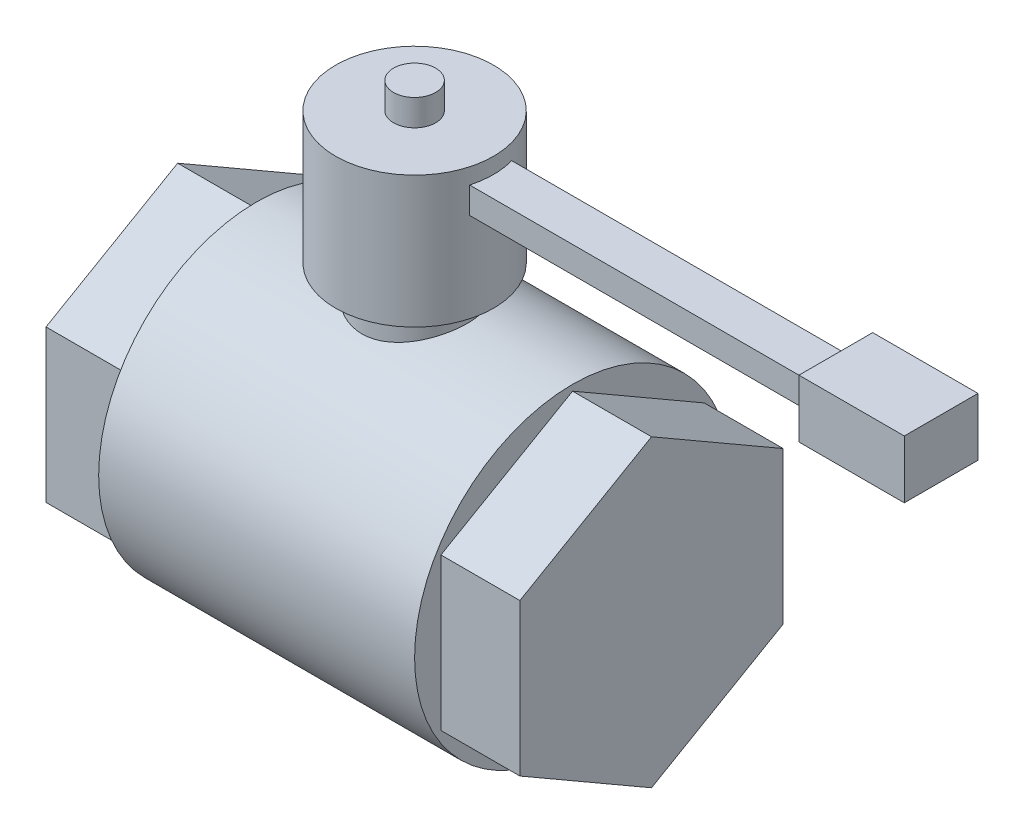
SolidWorks part; units mm, degrees
ref_plane "Плоскость1" through (0, 0, 0) normal (0, 0, 1) x (1, 0, 0)
ref_plane "Плоскость2" through (0, 0, 0) normal (0, 1, 0) x (1, 0, 0)
ref_plane "Плоскость3" through (0, 0, 0) normal (1, 0, 0) x (0, 0, -1)
sketch "Эскиз1" plane through (0, 0, 0) normal (1, 0, 0) x (0, 0, -1)
  line L1 (0, 28.8675) -> (-25, 14.4338)
  line L2 (-25, 14.4338) -> (-25, -14.4338)
  line L3 (-25, -14.4338) -> (0, -28.8675)
  line L4 (0, -28.8675) -> (25, -14.4338)
  line L5 (25, -14.4338) -> (25, 14.4338)
  line L6 (25, 14.4338) -> (0, 28.8675)
  circle A0 centre (0, 0) radius 25 construction
  dimension "D1" = 50
extrude "Основание-Вытянуть" add sketch "Эскиз1" along normal blind 15
sketch "Эскиз2" plane through (0, 0, 0) normal (-1, 0, 0) x (0, 0, 1)
  circle A0 centre (0, 0) radius 30
  dimension "D1" = 60
extrude "Бобышка-Вытянуть1" add sketch "Эскиз2" along normal blind 60
sketch "Эскиз3" plane through (-60, 0, 0) normal (-1, 0, 0) x (0, 0, 1)
  line L1 (0, 28.8675) -> (-25, 14.4338)
  line L2 (-25, 14.4338) -> (-25, -14.4338)
  line L3 (-25, -14.4338) -> (0, -28.8675)
  line L4 (0, -28.8675) -> (25, -14.4338)
  line L5 (25, -14.4338) -> (25, 14.4338)
  line L6 (25, 14.4338) -> (0, 28.8675)
  line L7 (0, 28.8675) -> (25, 14.4338) construction
  circle A0 centre (0, 0) radius 25 construction
extrude "Бобышка-Вытянуть2" add sketch "Эскиз3" along normal blind 15
sketch "Эскиз4" plane through (0, 0, 0) normal (0, 1, 0) x (1, 0, 0)
  line L0 (-60, 0) -> (0, 0) construction
  circle A0 centre (-30, 0) radius 10
  dimension "D1" = 20
extrude "Бобышка-Вытянуть3" add sketch "Эскиз4" along normal blind 35
sketch "Эскиз5" plane through (0, 35, 0) normal (0, 1, 0) x (-1, 0, 0)
  line L0 (60, 0) -> (0, 0) construction
  circle A0 centre (30, 0) radius 15
  circle A1 centre (30, 0) radius 10 construction
  dimension "D1" = 30
extrude "Бобышка-Вытянуть4" add sketch "Эскиз5" along normal blind 25
sketch "Эскиз6" plane through (0, 60, 0) normal (0, 1, 0) x (-1, 0, 0)
  line L0 (60, 0) -> (0, 0) construction
  circle A0 centre (30, 0) radius 4
  circle A1 centre (30, 0) radius 15 construction
  dimension "D1" = 8
extrude "Бобышка-Вытянуть5" add sketch "Эскиз6" along normal blind 5
ref_plane "Плоскость4" through (-30, 0, 0) normal (1, 0, 0) x (0, 0, -1)
sketch "Эскиз7" plane through (-30, 0, 0) normal (1, 0, 0) x (0, 0, -1)
  line L0 (0, 60) -> (0, 35) construction
  line L1 (-4, 57) -> (0, 57)
  line L2 (-4, 57) -> (-4, 52)
  line L3 (-4, 52) -> (4, 52)
  line L4 (4, 57) -> (4, 52)
  line L5 (15, 60) -> (-15, 60) construction
  line L6 (0, 57) -> (4, 57)
  dimension "D1" = 3
  dimension "D2" = 5
  dimension "D3" = 8
extrude "Бобышка-Вытянуть6" add sketch "Эскиз7" along normal blind 100
sketch "Эскиз8" plane through (70, 0, 0) normal (1, 0, 0) x (0, 0, -1)
  line L16 (-7, 60) -> (-7, 49)
  line L17 (-7, 49) -> (7, 49)
  line L18 (7, 49) -> (7, 60)
  line L19 (7, 60) -> (-7, 60)
  line L20 (-7, 60) -> (-7, 49)
  line L21 (-7, 49) -> (7, 49)
  line L22 (7, 49) -> (7, 60)
  line L23 (7, 60) -> (-7, 60)
  dimension "D1" = 3
extrude "Бобышка-Вытянуть7" add sketch "Эскиз8" against normal blind 20
ref_axis "Ось1" through (-108.8916, 0, 0) along (1, 0, 0)
